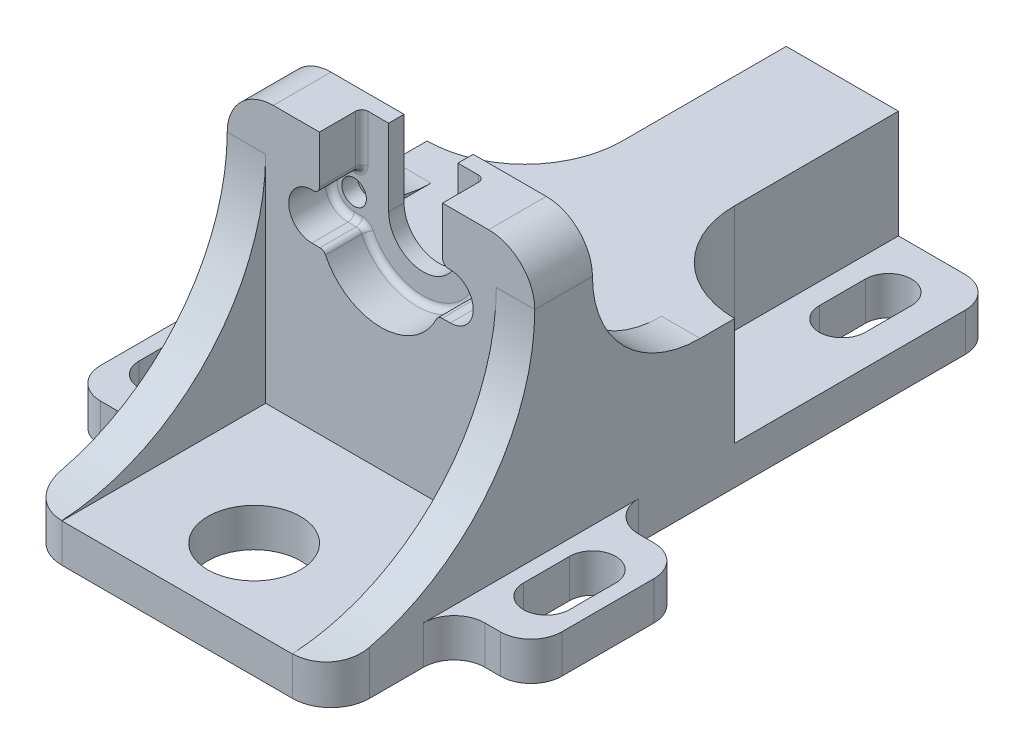
SolidWorks part; units mm, degrees
ref_plane "Front Plane" through (0, 0, 0) normal (0, 0, 1) x (1, 0, 0)
ref_plane "Top Plane" through (0, 0, 0) normal (0, 1, 0) x (1, 0, 0)
ref_plane "Right Plane" through (0, 0, 0) normal (1, 0, 0) x (0, 0, -1)
sketch "Sketch1" plane through (0, 0, 0) normal (0, 1, 0) x (1, 0, 0)
  line L1 (10, -25) -> (-10, -25)
  line L2 (10, -25) -> (10, 25)
  line L3 (10, 25) -> (-10, 25)
  line L4 (-10, -25) -> (-10, 25)
  line L5 (10, -25) -> (-10, 25) construction
  line L6 (10, 25) -> (-10, -25) construction
  point P0 (0, 0)
  dimension "D1" = 50
  dimension "D2" = 20
extrude "Boss-Extrude1" add sketch "Sketch1" along normal blind 9.525
sketch "Sketch2" plane through (0, 9.525, 0) normal (0, 1, 0) x (1, 0, 0)
  line L0 (-10, 25) -> (-10, -25) construction
  line L1 (-10, -1.25) -> (10, -1.25)
  line L2 (-10, -1.25) -> (-10, -5)
  line L3 (-10, -5) -> (10, -5)
  line L4 (10, -1.25) -> (10, -5)
  line L5 (10, -25) -> (10, 25) construction
  line L6 (-10, -25) -> (10, -25) construction
  dimension "D1" = 3.75
  dimension "D2" = 20
extrude "Boss-Extrude2" add sketch "Sketch2" along normal blind 10
sketch "Sketch3" plane through (0, 0, 5) normal (0, 0, 1) x (1, 0, 0)
  line L0 (-10, 19.525) -> (-10, 9.525) construction
  line L1 (-10, 9.525) -> (10, 9.525) construction
  line L2 (-10, 9.525) -> (-10, 19.525) construction
  line L3 (-10, 19.525) -> (10, 19.525) construction
  line L4 (10, 9.525) -> (10, 19.525) construction
  line L5 (-10, 9.525) -> (10, 19.525) construction
  line L6 (-10, 19.525) -> (10, 9.525) construction
  line L7 (-10, 9.525) -> (10, 9.525) construction
  line L8 (-4, 16.025) -> (-4, 19.525)
  line L9 (-4, 19.525) -> (4, 19.525)
  line L10 (4, 19.525) -> (4, 16.025)
  line L11 (0, 19.525) -> (0, 9.525) construction
  line L12 (-4.5, 14.525) -> (4.5, 14.525) construction
  line L13 (-4.5, 16.025) -> (-4, 16.025)
  line L14 (-4.5, 13.025) -> (-3.7081, 13.025)
  line L15 (4, 16.025) -> (4.5, 16.025)
  line L16 (3.7081, 13.025) -> (4.5, 13.025)
  line L17 (-4.5, 16.025) -> (-4.5, 13.025) construction
  arc A0 (-3.7081, 13.025) -> (3.7081, 13.025) centre (0, 14.525) ccw
  arc A3 (-4.5, 16.025) -> (-4.5, 13.025) centre (-4.5, 14.525) ccw
  arc A4 (4.5, 13.025) -> (4.5, 16.025) centre (4.5, 14.525) ccw
  point P20 (0, 11.35)
  dimension "D1" = 8
  dimension "D2" = 9
  dimension "D4" = 1.5
extrude "Cut-Extrude1" cut sketch "Sketch3" against normal offset from surface (2.75 mm away) 1 up to face at (2.5, 17.025, 1.25)
sketch "Sketch5" plane through (0, 0, 2.25) normal (0, 0, 1) x (1, 0, 0)
  line L0 (-2.25, 14.525) -> (-2.25, 19.525)
  line L1 (-4, 19.525) -> (4, 19.525) construction
  line L2 (-2.25, 19.525) -> (2.25, 19.525)
  line L3 (2.25, 19.525) -> (2.25, 14.525)
  arc A0 (-2.25, 14.525) -> (2.25, 14.525) centre (0, 14.525) ccw
  circle A1 centre (-4.5, 14.525) radius 0.8
  circle A2 centre (4.5, 14.525) radius 0.8
  dimension "D1" = 1.6
  dimension "D2" = 4.5
extrude "Cut-Extrude2" cut sketch "Sketch5" against normal through all
fillet "Fillet1" radius 0.4 13 edges at (4.104, 13.025, 2.25) (-4.104, 13.025, 2.25) (-4.25, 16.025, 2.25) (-4, 16.025, 3.625) (3.7081, 13.025, 3.625) (-3.7081, 13.025, 3.625) (6, 14.525, 2.25) (0, 10.525, 2.25) (-4, 17.775, 2.25) (-6, 14.525, 2.25) (4.25, 16.025, 2.25) (4, 16.025, 3.625) (4, 17.775, 2.25)
fillet "Fillet2" radius 3 2 edges at (10, 19.525, 3.125) (-10, 19.525, 3.125)
sketch "Sketch6" plane through (0, 9.525, 0) normal (0, 1, 0) x (1, 0, 0)
  line L2 (-10, -5) -> (10, -5)
  line L3 (-10, -5) -> (-10, -25)
  line L4 (-10, -25) -> (10, -25)
  line L5 (10, -5) -> (10, -25)
extrude "Cut-Extrude3" cut sketch "Sketch6" against normal offset from surface (7.025 mm away) 2.5 up to face at (0, 0, 0)
sketch "Sketch7" plane through (0, 2.5, 0) normal (0, 1, 0) x (1, 0, 0)
  line L1 (-2.25, -2.25) -> (2.25, -2.25) construction
  circle A0 centre (0, -13.25) radius 3.01
  dimension "D1" = 6.02
  dimension "D2" = 11
extrude "Cut-Extrude4" cut sketch "Sketch7" against normal through all
sketch "Sketch8" plane through (-10, 0, 0) normal (-1, 0, 0) x (0, 0, 1)
  line L0 (5, 16.525) -> (1.25, 16.525) construction
  line L1 (5, 2.5) -> (19.025, 2.5)
  line L2 (5, 2.5) -> (5, 16.525)
  line L4 (1.25, 9.525) -> (-5.75, 9.525)
  line L5 (1.25, 9.525) -> (1.25, 16.525)
  arc A0 (5, 16.525) -> (19.025, 2.5) centre (19.025, 16.525) ccw
  arc A1 (-5.75, 9.525) -> (1.25, 16.525) centre (-5.75, 16.525) ccw
extrude "Boss-Extrude3" add sketch "Sketch8" against normal blind 2.5
sketch "Sketch11" plane through (0, 9.525, 0) normal (0, 1, 0) x (1, 0, 0)
  line L0 (10, 25) -> (-10, 25) construction
  line L1 (-3.65, 25) -> (-10, 25)
  line L2 (-3.65, 25) -> (-3.65, 14.35)
  line L3 (-10, 25) -> (-10, 5.75) construction
  line L4 (-10, 25) -> (-10, 8)
  arc A0 (-10, 8) -> (-3.65, 14.35) centre (-10, 14.35) ccw
  dimension "D1" = 17
  dimension "D2" = 6.35
extrude "Cut-Extrude6" cut sketch "Sketch11" against normal up to surface (7.025 mm away) up to face at (-2.5, 2.5, 16.3417)
mirror "Mirror1" about plane through (0, 0, 0) normal (1, 0, 0) of "Cut-Extrude6", "Boss-Extrude3"
sketch "Sketch13" plane through (0, 0, 0) normal (0, -1, 0) x (1, 0, 0)
  line L0 (10, 25) -> (10, -25) construction
  line L1 (-10, 25) -> (10, 25)
  line L2 (-10, 25) -> (-10, 18.25)
  line L3 (-10, 18.25) -> (10, 18.25)
  line L4 (10, 25) -> (10, 18.25)
  circle A0 centre (0, 13.25) radius 3.01 construction
  dimension "D1" = 5
extrude "Cut-Extrude8" cut sketch "Sketch13" against normal through all
sketch "Sketch14" plane through (0, 0, 0) normal (0, -1, 0) x (1, 0, 0)
  line L0 (0, 23.25) -> (0, -25) construction
  line L1 (15, 0.24) -> (-15, 0.24)
  line L2 (15, 0.24) -> (15, 10.24)
  line L3 (15, 10.24) -> (-15, 10.24)
  line L4 (-15, 0.24) -> (-15, 10.24)
  line L5 (10, -25) -> (-10, -25) construction
  line L6 (-10, -25) -> (-10, 18.25) construction
  circle A1 centre (0, 13.25) radius 3.01 construction
  dimension "D1" = 10
  dimension "D2" = 5
extrude "Boss-Extrude4" add sketch "Sketch14" against normal up to surface (2.5 mm away) up to face at (0, 2.5, 11.625)
sketch "Sketch12" plane through (0, 2.5, 0) normal (0, 1, 0) x (1, 0, 0)
  line L0 (-6.5, 21.5) -> (-6.5, 18.5) construction
  line L1 (-5, 21.5) -> (-5, 18.5)
  line L2 (-8, 21.5) -> (-8, 18.5)
  line L3 (6.5, 21.5) -> (6.5, 18.5) construction
  line L4 (8, 21.5) -> (8, 18.5)
  line L5 (5, 21.5) -> (5, 18.5)
  line L6 (-12.5, -6.74) -> (-12.5, -3.74) construction
  line L7 (-14, -6.74) -> (-14, -3.74)
  line L8 (-11, -6.74) -> (-11, -3.74)
  line L9 (0, 25) -> (0, -25) construction
  line L10 (3.65, 25) -> (-3.65, 25) construction
  line L12 (-10, 8) -> (-10, 25) construction
  line L13 (-10, 25) -> (-3.65, 25) construction
  line L14 (12.5, -6.74) -> (12.5, -3.74) construction
  line L15 (11, -6.74) -> (11, -3.74)
  line L16 (14, -6.74) -> (14, -3.74)
  line L17 (15, -10.24) -> (10, -10.24) construction
  line L18 (10, -10.24) -> (15, -10.24) construction
  line L19 (10, -10.24) -> (10, -0.24) construction
  line L20 (10, -0.24) -> (15, -0.24) construction
  line L21 (15, -10.24) -> (15, -0.24) construction
  line L22 (10, -10.24) -> (15, -0.24) construction
  line L23 (10, -0.24) -> (15, -10.24) construction
  line L24 (10, -10.24) -> (10, -0.24) construction
  arc A0 (-5, 21.5) -> (-8, 21.5) centre (-6.5, 21.5) ccw
  arc A1 (-8, 18.5) -> (-5, 18.5) centre (-6.5, 18.5) ccw
  arc A2 (8, 21.5) -> (5, 21.5) centre (6.5, 21.5) ccw
  arc A3 (5, 18.5) -> (8, 18.5) centre (6.5, 18.5) ccw
  arc A4 (-14, -6.74) -> (-11, -6.74) centre (-12.5, -6.74) ccw
  arc A5 (-11, -3.74) -> (-14, -3.74) centre (-12.5, -3.74) ccw
  arc A6 (11, -6.74) -> (14, -6.74) centre (12.5, -6.74) ccw
  arc A7 (14, -3.74) -> (11, -3.74) centre (12.5, -3.74) ccw
  point P2 (-6.5, 20)
  point P7 (6.5, 20)
  point P16 (-12.5, -5.24)
  point P26 (12.5, -5.24)
  point P37 (12.5, -5.24)
  dimension "D1" = 1.5
  dimension "D5" = 3.5
  dimension "D2" = 3
  dimension "D4" = 2
extrude "Cut-Extrude7" cut sketch "Sketch12" against normal through all
fillet "Fillet3" radius 2 10 edges at (10, 1.25, -25) (-10, 1.25, -25) (-10, 1.25, 0.24) (-10, 1.25, 10.24) (10, 1.25, 10.24) (10, 1.25, 0.24) (15, 1.25, 0.24) (-15, 1.25, 0.24) (-15, 1.25, 10.24) (15, 1.25, 10.24)
fillet "Fillet4" radius 2.5 2 edges at (10, 1.2607, 18.25) (-10, 1.2607, 18.25)
